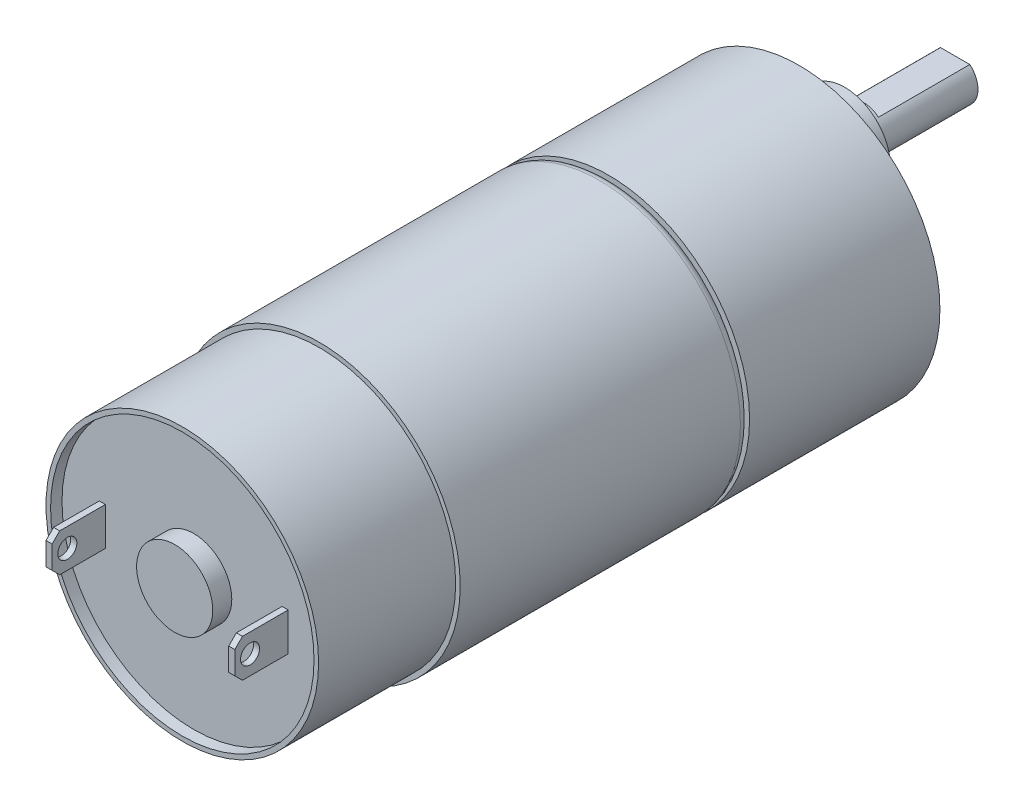
SolidWorks part; units mm, degrees
ref_plane "Front" through (0, 0, 0) normal (0, 0, 1) x (1, 0, 0)
ref_plane "Top" through (0, 0, 0) normal (0, 1, 0) x (1, 0, 0)
ref_plane "Right" through (0, 0, 0) normal (1, 0, 0) x (0, 0, -1)
sketch "Sketch1" plane through (0, 0, 0) normal (0, 0, 1) x (1, 0, 0)
  circle A0 centre (0, 0) radius 18.5
  dimension "D1" = 37
extrude "Boss-Extrude1" add sketch "Sketch1" along normal blind 25
sketch "Sketch2" plane through (0, 0, 25) normal (0, 0, 1) x (1, 0, 0)
  circle A1 centre (0, 0) radius 18.5
  circle A2 centre (0, 0) radius 18.5
  dimension "D1" = 0
extrude "Boss-Extrude2" add sketch "Sketch2" along normal blind 56 separate body
fillet "Fillet1" radius 1.2 1 edges at (18.5, 0, 25)
sketch "Sketch3" plane through (0, 0, 81) normal (0, 0, 1) x (1, 0, 0)
  circle A2 centre (0, 0) radius 17.9
  circle A5 centre (0, 0) radius 18.5 construction
  circle A6 centre (0, 0) radius 18.5
  dimension "D1" = 35.8
extrude "Cut-Extrude2" cut sketch "Sketch3" against normal blind 18
sketch "Sketch4" plane through (0, 0, 81) normal (0, 0, 1) x (1, 0, 0)
  circle A0 centre (0, 0) radius 17.3
  circle A1 centre (0, 0) radius 17.9
  circle A2 centre (0, 0) radius 17.9
  dimension "D1" = 0
  dimension "D2" = 0.6
extrude "Cut-Extrude3" cut sketch "Sketch4" against normal blind 1.5 contours A0
sketch "Sketch5" plane through (0, 0, 79.5) normal (0, 0, 1) x (1, 0, 0)
  circle A0 centre (0, 0) radius 5
  dimension "D1" = 10
extrude "Boss-Extrude3" add sketch "Sketch5" along normal blind 2.5
sketch "Sketch6" plane through (0, 0, 79.5) normal (0, 0, 1) x (1, 0, 0)
  line L1 (-12.4, -2.5) -> (-11.6, -2.5)
  line L2 (-12.4, -2.5) -> (-12.4, 2.5)
  line L3 (-12.4, 2.5) -> (-11.6, 2.5)
  line L4 (-11.6, -2.5) -> (-11.6, 2.5)
  line L5 (-12.4, -2.5) -> (-11.6, 2.5) construction
  line L6 (-12.4, 2.5) -> (-11.6, -2.5) construction
  line L7 (11.6, -2.5) -> (12.4, -2.5)
  line L8 (11.6, -2.5) -> (11.6, 2.5)
  line L9 (11.6, 2.5) -> (12.4, 2.5)
  line L10 (12.4, -2.5) -> (12.4, 2.5)
  line L11 (11.6, -2.5) -> (12.4, 2.5) construction
  line L12 (11.6, 2.5) -> (12.4, -2.5) construction
  point P0 (-12, 0)
  point P5 (12, 0)
  dimension "D1" = 5
  dimension "D2" = 0.8
  dimension "D3" = 5
  dimension "D4" = 0.8
  dimension "D5" = 12
  dimension "D6" = 12
extrude "Boss-Extrude4" add sketch "Sketch6" along normal blind 7
sketch "Sketch7" plane through (-12.4, 0, 0) normal (-1, 0, 0) x (0, 0, 1)
  line L0 (84.5, 0) -> (86.5, 0) construction
  line L1 (86.5, 2.5) -> (86.5, -2.5) construction
  circle A0 centre (84.5, 0) radius 1.25
  dimension "D1" = 2.5
  dimension "D2" = 2
extrude "Cut-Extrude4" cut sketch "Sketch7" against normal up to surface (24.8 mm away) up to face at (12.4, 0, 83)
chamfer "Chamfer1" distance 1 angle 45 4 edges at (-12, -2.5, 86.5) (-12, 2.5, 86.5) (12, -2.5, 86.5) (12, 2.5, 86.5)
sketch "Sketch8" plane through (0, 0, 0) normal (0, 0, -1) x (-1, 0, 0)
  circle A0 centre (0, 7) radius 6
  dimension "D1" = 12
  dimension "D2" = 7
extrude "Boss-Extrude5" add sketch "Sketch8" along normal blind 6
sketch "Sketch9" plane through (0, 0, -6) normal (0, 0, -1) x (-1, 0, 0)
  circle A1 centre (0, 7) radius 3
  dimension "D1" = 6
extrude "Boss-Extrude6" add sketch "Sketch9" along normal blind 2.5
sketch "Sketch10" plane through (0, 0, -8.5) normal (0, 0, -1) x (-1, 0, 0)
  line L0 (1.9261, 9.3) -> (-1.9261, 9.3)
  circle A1 centre (0, 7) radius 3
  circle A2 centre (0, 7) radius 3
  circle M3 centre (0, 7) radius 3
  dimension "D2" = 2.3
  dimension "D1" = 0
extrude "Boss-Extrude7" add sketch "Sketch10" along normal blind 12 contours L0 M3
sketch "Sketch11" plane through (0, 0, 0) normal (0, 0, -1) x (-1, 0, 0)
  circle A2 centre (0, 0) radius 12.5
  arc A3 (-7.3795, 10.0893) -> (7.3795, 10.0893) centre (0, 0) ccw
  circle A5 centre (0, 7) radius 8
  arc A6 (-7.3795, 10.0893) -> (7.3795, 10.0893) centre (0, 7) ccw
  dimension "D1" = 6
  dimension "D2" = 2
extrude "Cut-Extrude5" cut sketch "Sketch11" against normal blind 0.6
fillet "Fillet2" radius 0.2 4 edges at (0, -1, 0.6) (0, -1, 0) (0, -12.5, 0.6) (0, -12.5, 0)
sketch "Sketch12" plane through (0, 0, 0) normal (0, 0, -1) x (-1, 0, 0)
  line L0 (-18.5, 0) -> (0, 0) construction
  line L1 (-9.25, 16.0215) -> (0, 0) construction
  line L2 (9.25, 16.0215) -> (0, 0) construction
  line L3 (18.5, 0) -> (0, 0) construction
  line L4 (9.25, -16.0215) -> (0, 0) construction
  line L5 (-9.25, -16.0215) -> (0, 0) construction
  circle A0 centre (0, 0) radius 18.5 construction
  circle A1 centre (-15.5, 0) radius 1.5
  circle A2 centre (-7.75, 13.4234) radius 1.5
  circle A3 centre (7.75, 13.4234) radius 1.5
  circle A4 centre (15.5, 0) radius 1.5
  circle A5 centre (7.75, -13.4234) radius 1.5
  circle A6 centre (-7.75, -13.4234) radius 1.5
  point P24 (0, 0)
  dimension "D1" = 3
  dimension "D2" = 15.5
  dimension "D3" = 6
extrude "Cut-Extrude6" cut sketch "Sketch12" against normal blind 4
